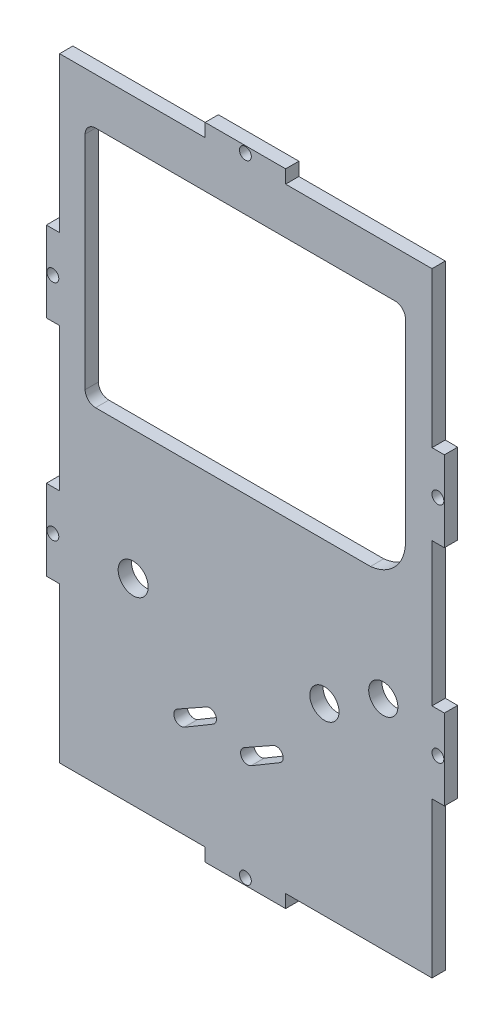
SolidWorks part; units mm, degrees
ref_plane "Front Plane" through (0, 0, 0) normal (0, 0, 1) x (1, 0, 0)
ref_plane "Top Plane" through (0, 0, 0) normal (0, 1, 0) x (1, 0, 0)
ref_plane "Right Plane" through (0, 0, 0) normal (1, 0, 0) x (0, 0, -1)
sketch "Sketch1" plane through (0, 0, 0) normal (0, 0, 1) x (1, 0, 0)
  line L0 (0.1058, 73.6301) -> (-0.0148, 62.4901) construction
  line L1 (-0.0148, 62.4901) -> (-0.0148, 56.2001) construction
  line L2 (-0.0148, 56.2001) -> (-0.0148, 10.268) construction
  line L3 (-15.4692, -49.8142) -> (-8.5409, -45.8142) construction
  line L4 (-15.4692, -49.8142) -> (0.5308, -49.8142) construction
  line L5 (0.5308, -49.8142) -> (7.4591, -45.8142) construction
  line L6 (-0.0148, 10.268) -> (0.1058, -73.6642) construction
  line L15 (-16.3293, -29.1587) -> (-16.3293, -23.8757)
  line L20 (-0.2968, -48.3429) -> (6.6759, -44.4208)
  line L21 (8.2583, -47.1985) -> (1.3584, -51.2855)
  line L22 (-44.5392, 73.6301) -> (44.7508, 73.6301)
  line L23 (44.7508, 73.6301) -> (44.7508, -73.6642)
  line L24 (44.7508, -73.6642) -> (-44.5392, -73.6642)
  line L25 (-44.5392, -73.6642) -> (-44.5392, 73.6301)
  line L26 (-25.0598, 56.2001) -> (-25.0598, 10.268)
  line L27 (-25.0598, 10.268) -> (25.0303, 10.268)
  line L28 (25.0303, 10.268) -> (25.0303, 56.2001)
  line L29 (25.0303, 56.2001) -> (-25.0598, 56.2001)
  line L34 (35.8896, 62.4901) -> (-35.9192, 62.4901)
  line L35 (-38.4192, 59.9901) -> (-38.4192, 6.918)
  line L36 (-35.9192, 4.418) -> (29.9974, 4.418)
  line L37 (38.3896, 13.668) -> (38.3896, 59.9901)
  line L38 (-16.2968, -48.3429) -> (-9.3241, -44.4208)
  line L39 (-7.7417, -47.1985) -> (-14.6416, -51.2855)
  line L150 (42.2525, -55.0539) -> (42.2511, -54.9499)
  circle A2 centre (-26.9008, -26.5172) radius 3.6
  arc A3 (8.2583, -47.1985) -> (6.6759, -44.4208) centre (7.4591, -45.8142) ccw
  arc A6 (-16.2968, -48.3429) -> (-14.6416, -51.2855) centre (-15.4692, -49.8142) ccw
  arc A7 (-7.7417, -47.1985) -> (-9.3241, -44.4208) centre (-8.5409, -45.8142) ccw
  circle A15 centre (18.9576, -29.5613) radius 3.5
  circle A16 centre (33.0683, -21.4917) radius 3.5
  arc A17 (-0.2968, -48.3429) -> (1.3584, -51.2855) centre (0.5308, -49.8142) ccw
  circle A19 centre (-32.8459, 40.326) radius 4.5
  arc A24 (38.3896, 59.9901) -> (35.8896, 62.4901) centre (35.8896, 59.9901) ccw
  arc A25 (-35.9192, 62.4901) -> (-38.4192, 59.9901) centre (-35.9192, 59.9901) ccw
  arc A26 (-38.4192, 6.918) -> (-35.9192, 4.418) centre (-35.9192, 6.918) ccw
  arc A27 (29.9974, 4.418) -> (38.3896, 13.668) centre (29.1397, 13.6282) ccw
  dimension "D4" = 11.14
  dimension "D8" = 7
  dimension "D11" = 9
  dimension "D12" = 7.2
  dimension "D14" = 9.25
  dimension "D15" = 2.5
  dimension "D2" = 89.29
  dimension "D3" = 147.2943
  dimension "D5" = 25.9097
  dimension "D6" = 8.0696
  dimension "D7" = 14.1107
  dimension "D9" = 7.7861
  dimension "D10" = 22.1641
  dimension "D13" = 10.5715
  dimension "D16" = 6.29
  dimension "D17" = 6.12
  dimension "D18" = 5.85
  dimension "D19" = 16
  dimension "D20" = 8
  dimension "D21" = 29.07
  dimension "D22" = 23.85
  dimension "D23" = 30
extrude "Body" add sketch "Sketch1<7>" along normal blind 3.18 contours L25 L24 L23 L22 A27 L36 A26 L35 A25 L34 A24 L37 A17 L20 A3 L21 A16 A15 A7 L39 A6 L38 A2 region at (0.1688, -16.746, 0)
sketch "Sketch1<7>" plane through (0, 0, 0) normal (0, 0, 1) x (1, 0, 0) same geometry as "Sketch1"
extrude "Buttons" [suppressed] add sketch "Sketch1" along normal blind 3.18 contours A19 | A2 | L39 A7 L38 A6 | L20 A17 L21 A3 | A15 | A16
sketch "Sketch2" plane through (0, 73.6301, 0) normal (0, 1, 0) x (1, 0, 0)
  line L0 (-9.65, 0) -> (9.65, 0)
  line L1 (-44.5392, 0) -> (44.7508, 0) construction
  line L2 (9.65, 0) -> (9.65, -3.18)
  line L3 (-44.5392, -3.18) -> (44.7508, -3.18) construction
  line L4 (9.65, -3.18) -> (-9.65, -3.18)
  line L5 (-9.65, -3.18) -> (-9.65, 0)
  line L6 (0, 0) -> (0, -3.18) construction
  dimension "D1" = 19.3
extrude "Boss-Extrude1" add sketch "Sketch2" along normal blind 3.18
sketch "Sketch3" plane through (0, 0, 3.18) normal (0, 0, 1) x (1, 0, 0)
  line L0 (-9.65, 75.2201) -> (9.65, 75.2201) construction
  line L1 (-9.65, 76.8101) -> (-9.65, 73.6301) construction
  line L2 (9.65, 76.8101) -> (9.65, 73.6301) construction
  line L3 (0, 76.8101) -> (0, 73.4734) construction
  line L4 (-9.65, 76.8101) -> (9.65, 76.8101) construction
  circle A0 centre (0, 75.2201) radius 1.425
extrude "Cut-Extrude1" cut sketch "Sketch3" against normal through all
sketch "Sketch4" plane through (-44.5392, 0, 0) normal (-1, 0, 0) x (0, 0, 1)
  line L0 (0, 17.1601) -> (0, 36.4601)
  line L1 (0, -73.6642) -> (0, 73.6301) construction
  line L2 (0, 36.4601) -> (3.18, 36.4601)
  line L3 (3.18, -73.6642) -> (3.18, 73.6301) construction
  line L4 (3.18, 36.4601) -> (3.18, 17.1601)
  line L5 (3.18, 17.1601) -> (0, 17.1601)
  line L6 (3.18, 26.8101) -> (0, 26.8101) construction
  line L7 (0, 73.6301) -> (3.18, 73.6301) construction
  dimension "D1" = 19.3
  dimension "D2" = 46.82
extrude "Boss-Extrude2" add sketch "Sketch4" along normal blind 3.18
sketch "Sketch5" plane through (0, 0, 3.18) normal (0, 0, 1) x (1, 0, 0)
  line L0 (-47.7192, 26.8101) -> (-44.6033, 26.8101) construction
  line L1 (-47.7192, 17.1601) -> (-47.7192, 36.4601) construction
  line L2 (-46.1292, 17.1601) -> (-46.1292, 36.4601) construction
  line L3 (-47.7192, 17.1601) -> (-44.5392, 17.1601) construction
  line L4 (-47.7192, 36.4601) -> (-44.5392, 36.4601) construction
  circle A0 centre (-46.1612, 26.8101) radius 1.425
extrude "Cut-Extrude2" cut sketch "Sketch5" against normal through all
mirror "Mirror1" about plane through (0, 0, 0) normal (1, 0, 0) of "Cut-Extrude2", "Boss-Extrude2"
mirror "Mirror2" about plane through (0, 0, 0) normal (0, 1, 0) of "Cut-Extrude1", "Boss-Extrude1", "Mirror1"
